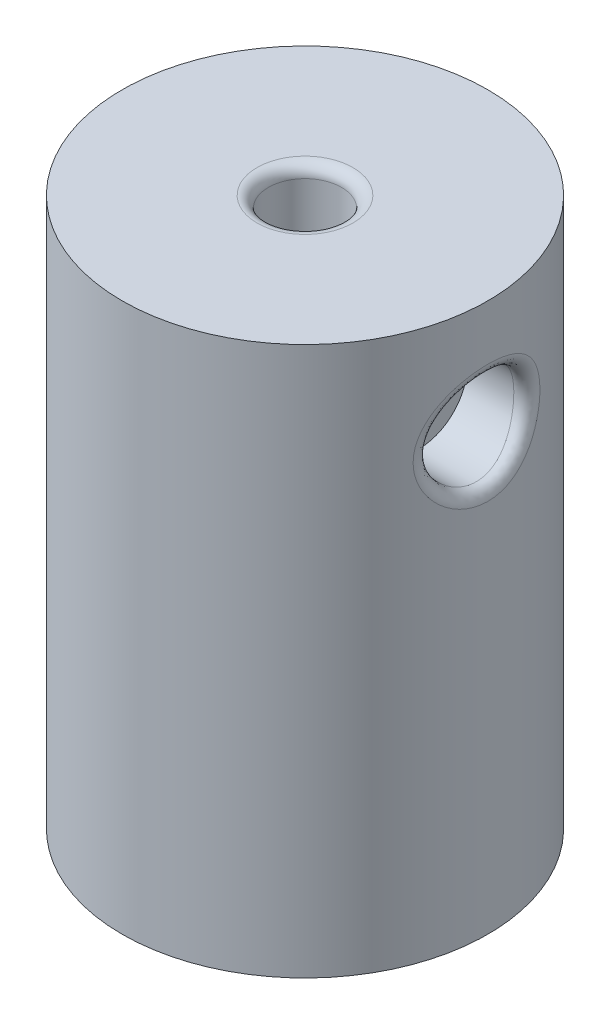
SolidWorks part; units mm, degrees
ref_plane "Front Plane" through (0, 0, 0) normal (0, 0, 1) x (1, 0, 0)
ref_plane "Top Plane" through (0, 0, 0) normal (0, 1, 0) x (1, 0, 0)
ref_plane "Right Plane" through (0, 0, 0) normal (1, 0, 0) x (0, 0, -1)
sketch "Sketch1" plane through (0, 0, 0) normal (0, 1, 0) x (1, 0, 0)
  circle A0 centre (0, 0) radius 8
  dimension "D1" = 16
extrude "Boss-Extrude1" add sketch "Sketch1" along normal blind 24
sketch "Sketch2" plane through (0, 24, 0) normal (0, 1, 0) x (1, 0, 0)
  circle A0 centre (0, 0) radius 1.6
  dimension "D1" = 3.2
extrude "Cut-Extrude1" cut sketch "Sketch2" against normal blind 12
sketch "Sketch3" plane through (0, 0, 0) normal (1, 0, 0) x (0, 0, -1)
  line L0 (-8, 24) -> (-8, 0) construction
  line L1 (8, 24) -> (-8, 24) construction
  circle A0 centre (0, 19) radius 0.95
  dimension "D2" = 1.9
  dimension "D1" = 8
  dimension "D3" = 5
extrude "Cut-Extrude2" cut sketch "Sketch3" along normal up to surface (6.4 mm away) from surface
sketch "Sketch4" plane through (0, 0, 0) normal (1, 0, 0) x (0, 0, -1)
  line L0 (1.6, 24) -> (-1.6, 24) construction
  circle A0 centre (0, 19) radius 2.1
  dimension "D2" = 4.2
  dimension "D1" = 5
extrude "Cut-Extrude3" cut sketch "Sketch4" along normal blind 10 from offset 5
fillet "Fillet1" radius 0.5 3 edges at (5, 19.2184, -0.9246) (7.73, 19.4042, -2.0607) (0, 24, 1.6)
